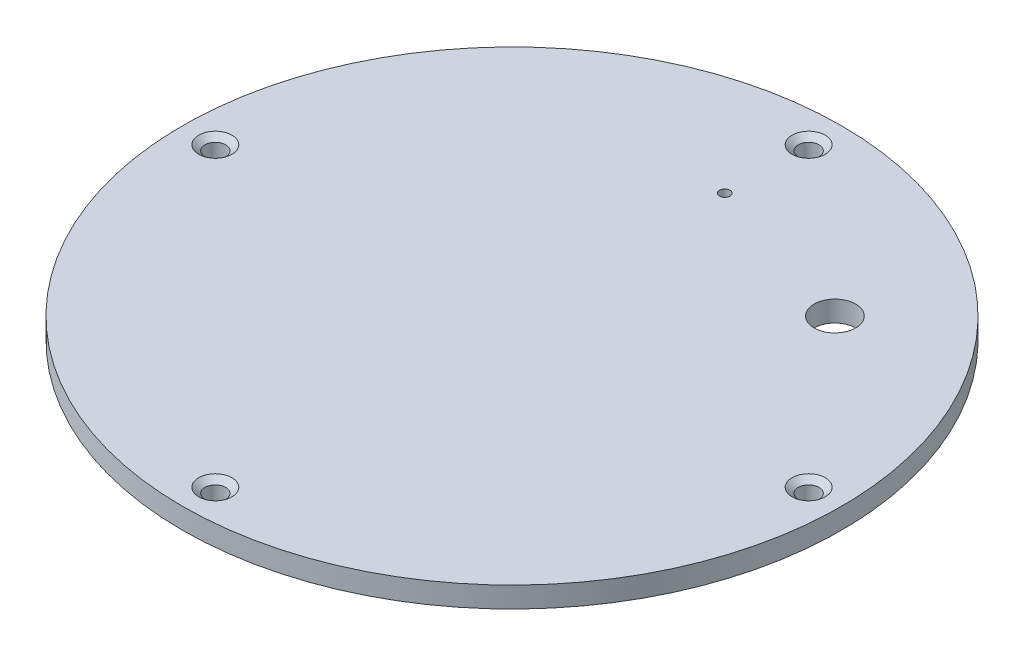
SolidWorks part; units mm, degrees
material "1060 Alloy"
ref_plane "Front Plane" through (0, 0, 0) normal (0, 0, 1) x (1, 0, 0)
ref_plane "Top Plane" through (0, 0, 0) normal (0, 1, 0) x (1, 0, 0)
ref_plane "Right Plane" through (0, 0, 0) normal (1, 0, 0) x (0, 0, -1)
sketch "Sketch1" plane through (0, 0, 0) normal (0, 1, 0) x (1, 0, 0)
  circle A0 centre (0, 0) radius 15.875
  dimension "D1" = 31.75
extrude "Boss-Extrude1" add sketch "Sketch1" along normal blind 1
hole_wizard "CSK for M2 Flat Head Machine Screw1" positions "Sketch2" profile "Sketch3" countersink size "M2" standard "ANSI Metric" end condition through all
sketch "Sketch2" plane through (0, 1, 0) normal (0, 1, 0) x (1, 0, 0)
  point P0 (0, 14.29)
  point P2 (14.29, 0)
  point P4 (0, -14.29)
  point P6 (-14.29, 0)
  dimension "D1" = 14.29
  dimension "D2" = 14.29
  dimension "D3" = 14.29
  dimension "D4" = 14.29
sketch "Sketch3" plane through (0, 1, -14.29) normal (1, 0, 0) x (0, 0, 1)
  line L0 (0, 0) -> (0, 1)
  line L1 (0, 1) -> (0.5, 1)
  line L2 (0.5, 1) -> (0.5, 0.2517)
  line L3 (0.5, 0.2517) -> (0.8, 0)
  line L5 (0.8, 0) -> (0, 0)
  line L6 (-0.5, 0.2517) -> (-0.8, 0) construction
  line L11 (0, -6.35) -> (0, 107.95) construction
  dimension "Thru Hole Dia." = 1
  dimension "Thru Hole Depth" = 1
  dimension "Near C'Sink Dia." = 1.6
  dimension "Near C'Sink Angle" = 100
sketch "Sketch5" plane through (0, 1, 0) normal (0, 1, 0) x (1, 0, 0)
  line L0 (0, 0) -> (12.6106, 12.6106) construction
  line L1 (0, 0) -> (20.4022, 0) construction
  circle A0 centre (0, 10.25) radius 0.25
  circle A1 centre (7.7782, 7.7782) radius 1
  dimension "D1" = 0.5
  dimension "D2" = 10.25
  dimension "D3" = 2
  dimension "D4" = 11
  dimension "D5" = 45
extrude "Cut-Extrude1" cut sketch "Sketch5" against normal through all both and the other way through all
